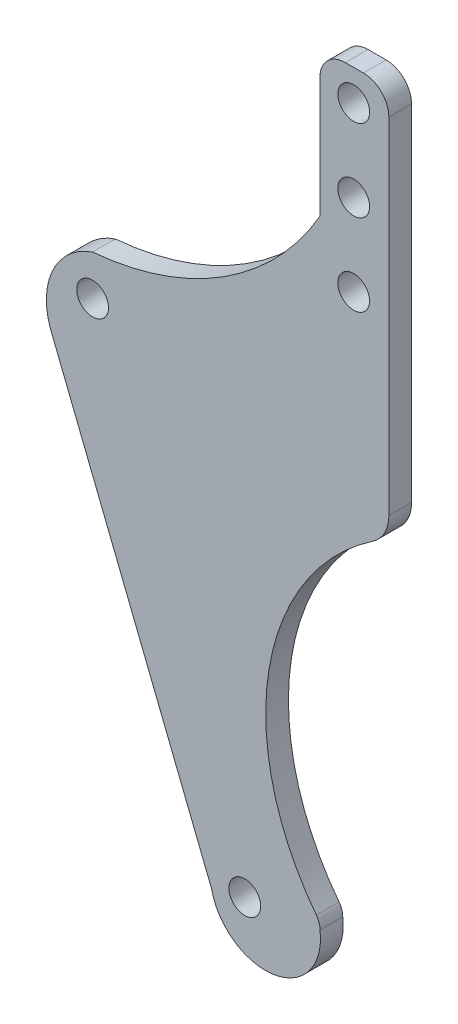
SolidWorks part; units mm, degrees
ref_plane "Front Plane" through (0, 0, 0) normal (0, 0, 1) x (1, 0, 0)
ref_plane "Top Plane" through (0, 0, 0) normal (0, 1, 0) x (1, 0, 0)
ref_plane "Right Plane" through (0, 0, 0) normal (1, 0, 0) x (0, 0, -1)
sketch "Sketch1" plane through (0, 0, 0) normal (0, 0, 1) x (1, 0, 0)
  line L0 (0, 0) -> (0, 30.156) construction
  line L1 (0, 0) -> (32.4691, 0) construction
  line L3 (-23.7777, 22.847) -> (-23.7777, 6.1258)
  line L4 (-17.6931, 26.403) -> (-20.2217, 26.403)
  line L5 (-61.5043, -26.2601) -> (-38.9095, -82.9749)
  line L7 (-14.1371, -25.3963) -> (-14.1371, 22.847)
  line L8 (-38.9095, -82.9749) -> (-24.2809, -78.8021) construction
  circle A0 centre (-55.5441, -19.825) radius 2.2225
  circle A1 centre (-19.05, 22.085) radius 2.2225
  circle A2 centre (-19.05, -0.775) radius 2.2225
  arc A3 (-23.8325, 5.9218) -> (-55.5441, -14.196) centre (-58.987, 26.2833) cw
  arc A5 (-23.7777, 6.1258) -> (-23.8325, 5.9218) centre (-24.1847, 6.1258) cw
  arc A6 (-17.6931, 26.403) -> (-14.1371, 22.847) centre (-17.6931, 22.847) cw
  arc A7 (-20.2217, 26.403) -> (-23.7777, 22.847) centre (-20.2217, 22.847) ccw
  arc A9 (-16.357, -29.5947) -> (-24.2809, -78.8021) centre (2.9569, -57.9465) ccw
  arc A11 (-16.357, -29.5947) -> (-14.1371, -25.3963) centre (-19.2171, -25.3963) ccw
  circle A14 centre (-34.2687, -81.6511) radius 2.2225
  arc A17 (-23.7579, -80.3848) -> (-24.2809, -78.8021) centre (-26.2976, -80.3463) ccw
  arc A21 (-38.9095, -82.9749) -> (-23.7579, -80.3848) centre (-31.383, -81.391) ccw
  arc A23 (-61.5043, -26.2601) -> (-55.5441, -14.196) centre (-52.4922, -23.2082) cw
  circle A24 centre (-19.05, 10.655) radius 2.2225
  point P14 (-18.9574, 26.403)
  point P24 (-15.2948, 26.5068)
  point P41 (-55.5441, -14.196)
  dimension "D1" = 4.445
  dimension "D2" = 40.6255
  dimension "D3" = 0.407
  dimension "D4" = 3.556
  dimension "D5" = 34.3053
  dimension "D6" = 5.08
  dimension "D7" = 2.54
  dimension "D11" = 14.1371
  dimension "D12" = 15.2948
  dimension "D13" = 18.9574
  dimension "D10" = 2.9569
  dimension "D14" = 23.8325
  dimension "D15" = 19.05
  dimension "D18" = 5.9218
  dimension "D19" = 26.403
  dimension "D21" = 26.5068
  dimension "D22" = 19.825
  dimension "D23" = 31.383
  dimension "D24" = 34.2687
  dimension "D8" = 7.6913
  dimension "D9" = 9.5149
  dimension "D31" = 4.445
  dimension "D16" = 24.2809
  dimension "D17" = 23.7579
  dimension "D20" = 22.085
  dimension "D25" = 38.9095
  dimension "D26" = 52.4922
  dimension "D27" = 55.5441
  dimension "D28" = 25.3963
  dimension "D29" = 61.5043
  dimension "D30" = 0.775
  dimension "D32" = 11.43
  dimension "D33" = 4.7277
extrude "Boss-Extrude1" add sketch "Sketch1" along normal blind 3.175
